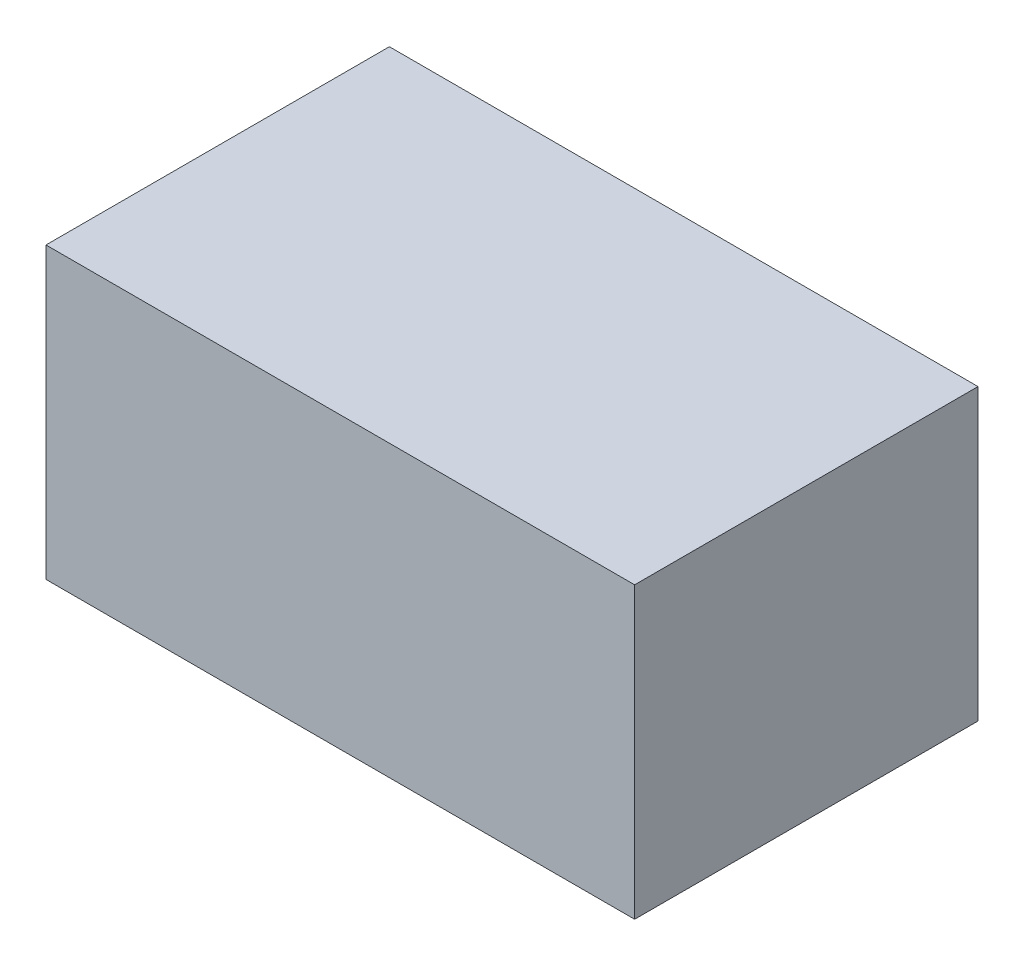
SolidWorks part; units mm, degrees
ref_plane "Front Plane" through (0, 0, 0) normal (0, 0, 1) x (1, 0, 0)
ref_plane "Top Plane" through (0, 0, 0) normal (0, 1, 0) x (1, 0, 0)
ref_plane "Right Plane" through (0, 0, 0) normal (1, 0, 0) x (0, 0, -1)
sketch "Sketch1" plane through (0, 0, 0) normal (0, 1, 0) x (1, 0, 0)
  line L1 (-762, 444.5) -> (762, 444.5)
  line L2 (-762, 444.5) -> (-762, -444.5)
  line L3 (-762, -444.5) -> (762, -444.5)
  line L4 (762, 444.5) -> (762, -444.5)
  line L5 (-762, 444.5) -> (762, -444.5) construction
  line L6 (-762, -444.5) -> (762, 444.5) construction
  point P0 (0, 0)
  dimension "D1" = 1524
  dimension "D2" = 889
extrude "Boss-Extrude1" add sketch "Sketch1" along normal blind 750
